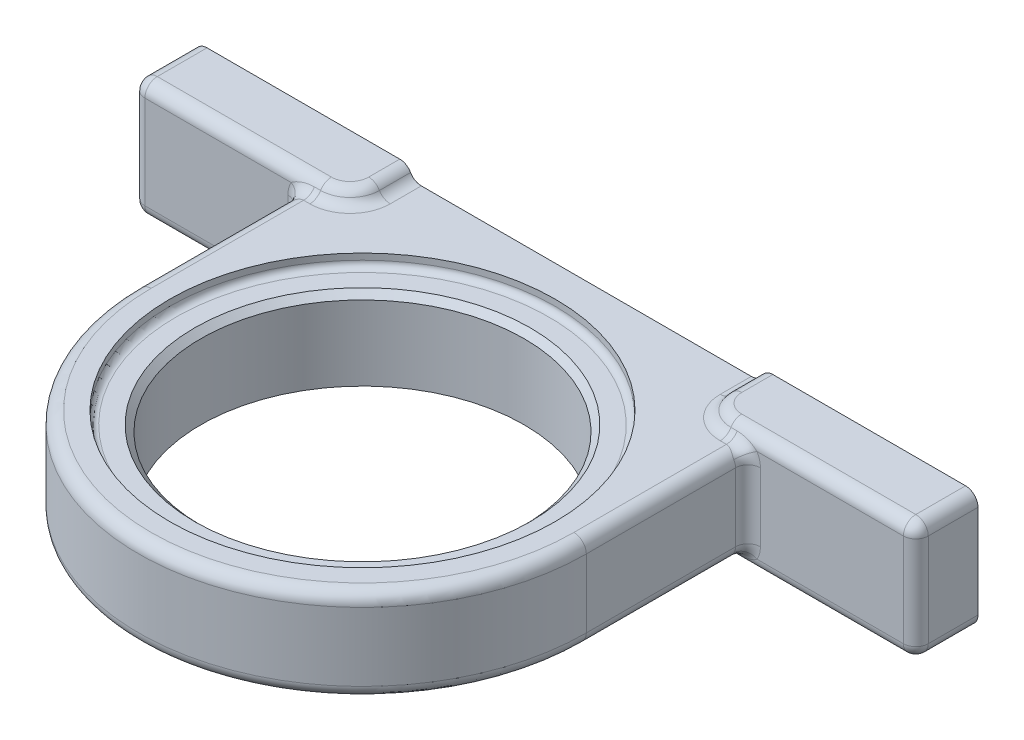
SolidWorks part; units mm, degrees
ref_plane "Front Plane" through (0, 0, 0) normal (1, 0, 0) x (0, 1, 0)
ref_plane "Top Plane" through (0, 0, 0) normal (0, 0, 1) x (0, 1, 0)
ref_plane "Right Plane" through (0, 0, 0) normal (0, 1, 0) x (-1, 0, 0)
sketch "Sketch1" plane through (0, 0, 0) normal (0, 1, 0) x (-1, 0, 0)
  line L0 (0, 72) -> (0, 62)
  line L1 (-36, 36) -> (-36, 0)
  line L2 (-36, 0) -> (0, 0)
  line L3 (0, 10) -> (0, 0)
  arc A0 (0, 62) -> (0, 10) centre (0, 36) ccw
  arc A1 (0, 72) -> (-36, 36) centre (0, 36) ccw
  point P1 (-7.6288, 57.0504)
  point P2 (0, 0)
  point P8 (0, 0)
  dimension "D1" = 52
  dimension "D2" = 10
  dimension "D3" = 10
extrude "Boss-Extrude1" add sketch "Sketch1" along normal blind 15
sketch "Sketch2" plane through (0, 15, 0) normal (0, 1, 0) x (-1, 0, 0)
  arc A2 (0, 67) -> (0, 5) centre (0, 36) ccw
  arc A3 (0, 67) -> (0, 5) centre (0, 36) ccw
  dimension "D1" = 5
extrude "Cut-Extrude-Thin1" cut sketch "Sketch2" against normal blind 2 and the other way through all thin contours A3 thin type one direction reverse wall 10
fillet "Fillet1" radius 1 1 edges at (31, 13, 36)
chamfer "Chamfer1" distance 1 angle 45 1 edges at (26, 13, 36)
fillet "Fillet5" radius 2 4 edges at (25.4558, 0, 61.4558) (25.4558, 15, 61.4558) (36, 0, 18) (36, 15, 18)
sketch "Sketch3" plane through (0, 0, 0) normal (0, 0, -1) x (1, 0, 0)
  line L0 (36, -13) -> (36, -2) construction
  line L1 (28, 2) -> (63, 2)
  line L2 (28, 2) -> (28, -17)
  line L3 (28, -17) -> (63, -17)
  line L4 (63, 2) -> (63, -17)
  point P6 (36, -7.5)
  point P7 (28, -7.5)
  dimension "D1" = 2
  dimension "D2" = 8
  dimension "D3" = 35
extrude "Boss-Extrude2" add sketch "Sketch3" against normal blind 10 separate body
fillet "Fillet2" radius 5 1 edges at (28, 7.5, 10)
fillet "Fillet3" radius 2 1 edges at (63, 7.5, 10)
fillet "Fillet4" radius 2 10 edges at (63, -2, 4) (62.4142, -2, 9.4142) (28, -2, 2.5) (29.4645, -2, 8.5355) (28, 17, 2.5) (29.4645, 17, 8.5355) (63, 17, 4) (62.4142, 17, 9.4142) (47, -2, 10) (47, 17, 10)
combine bodies "Combine1" operation type add bodies to combine 102 103
fillet "Fillet6" radius 2 9 edges at (28, 15, 2.5) (29.4645, 15, 8.5355) (33.5, 15, 10) (35.4142, 14.4142, 10) (28, 0, 2.5) (29.4645, 0, 8.5355) (33.5, 0, 10) (35.4142, 0.5858, 10) (36, 7.5, 10)
mirror "Mirror1" about plane through (0, 0, 0) normal (1, 0, 0) of bodies 104
